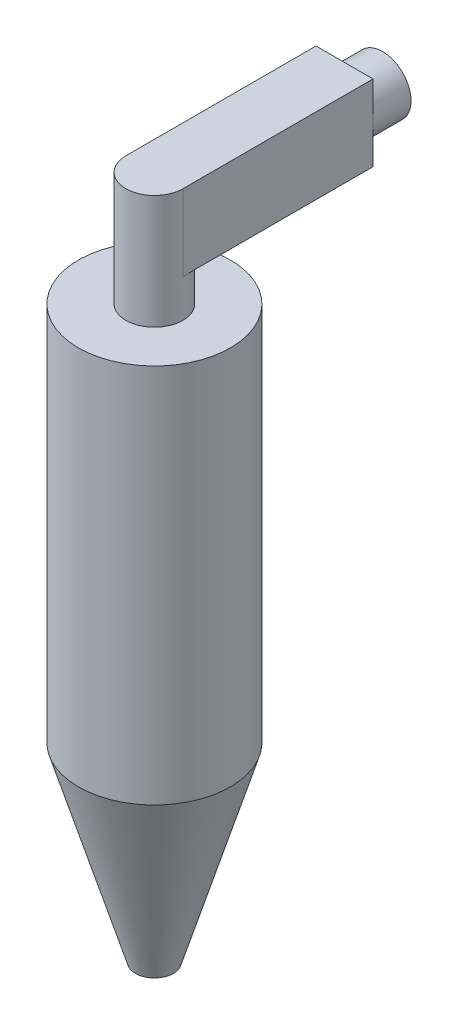
SolidWorks part; units mm, degrees
ref_plane "Front Plane" through (0, 0, 0) normal (0, 0, 1) x (1, 0, 0)
ref_plane "Top Plane" through (0, 0, 0) normal (0, 1, 0) x (1, 0, 0)
ref_plane "Right Plane" through (0, 0, 0) normal (1, 0, 0) x (0, 0, -1)
sketch "Sketch_Nuzzle Vent" plane through (0, 0, 0) normal (0, 1, 0) x (1, 0, 0)
  line L0 (0, 0) -> (0, 5) construction
  circle A0 centre (0, 0) radius 5
  point P11 (0, 5)
  dimension "D2" = 10
ref_plane "Plane_Nuzzle Neck" through (0, 50, 0) normal (0, 1, 0) x (1, 0, 0)
sketch "Sketch_Nuzzle Path" plane through (0, 50, 0) normal (0, 1, 0) x (1, 0, 0)
  line L0 (0, 0) -> (0, 20) construction
  circle A0 centre (0, 0) radius 20
  point P8 (0, 20)
  dimension "D1" = 40
loft "Loft_Nuzzle" add profiles "Sketch_Nuzzle Path", "Sketch_Nuzzle Vent" connector at (0.1131, 50, -19.9997) connector at (-0.0377, 0, -4.9999)
sketch "Sketch_Nuzzle Neck" plane through (0, 50, 0) normal (0, 1, 0) x (1, 0, 0)
  circle A1 centre (0, 0) radius 20
  circle A2 centre (0, 0) radius 20
  dimension "D1" = 0
extrude "Nuzzle Neck" add sketch "Sketch_Nuzzle Neck" along normal blind 100
ref_plane "Plane_Linkage" through (0, 150, 0) normal (0, 1, 0) x (1, 0, 0)
sketch "Sketch_Linkage" plane through (0, 150, 0) normal (0, 1, 0) x (1, 0, 0)
  circle A0 centre (0, 0) radius 7.5
  dimension "D1" = 15
extrude "Linkage" add sketch "Sketch_Linkage" along normal blind 30
sketch "Sketch_Linkage Neck" plane through (0, 0, 0) normal (0, 0, 1) x (1, 0, 0)
  line L0 (7.5, 180) -> (-7.5, 180) construction
  line L1 (-7.5, 180) -> (7.5, 180)
  line L2 (-7.5, 180) -> (-7.5, 160)
  line L3 (-7.5, 160) -> (7.5, 160)
  line L4 (7.5, 180) -> (7.5, 160)
  line L5 (-7.5, 180) -> (-7.5, 150) construction
  line L6 (7.5, 150) -> (7.5, 180) construction
  dimension "D1" = 20
extrude "Linkage Neck" add sketch "Sketch_Linkage Neck" against normal blind 50
ref_plane "Plane_Linkage Pivot" through (0, 0, -50) normal (0, 0, -1) x (-1, 0, 0)
sketch "Sketch_Linkage Pivot" plane through (0, 0, -50) normal (0, 0, -1) x (-1, 0, 0)
  line L0 (-7.5, 170) -> (7.5, 170) construction
  line L1 (-7.5, 160) -> (-7.5, 180) construction
  line L2 (7.5, 180) -> (7.5, 160) construction
  circle A0 centre (0, 170) radius 7.5
  point P8 (0, 0)
extrude "Linkage Pivot" add sketch "Sketch_Linkage Pivot" along normal blind 10
